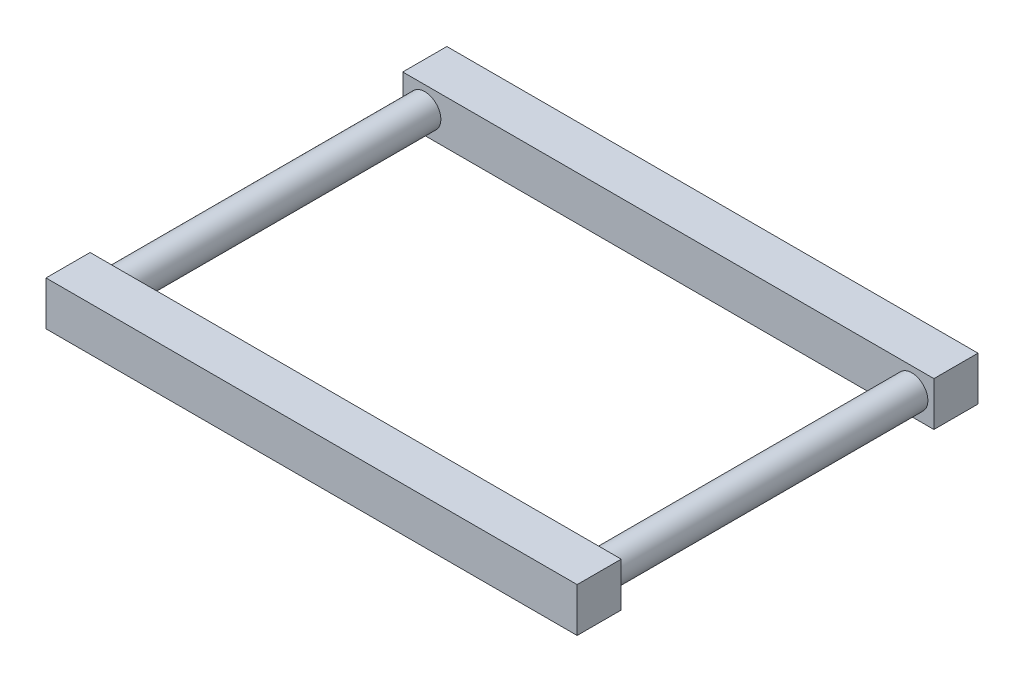
SolidWorks part; units mm, degrees
ref_plane "Front Plane" through (0, 0, 0) normal (0, 0, 1) x (1, 0, 0)
ref_plane "Top Plane" through (0, 0, 0) normal (0, 1, 0) x (1, 0, 0)
ref_plane "Right Plane" through (0, 0, 0) normal (1, 0, 0) x (0, 0, -1)
sketch "Sketch2" plane through (0, 0, 0) normal (0, 1, 0) x (1, 0, 0)
  line L0 (0, 0) -> (0, 198.12)
  line L1 (0, 0) -> (0, -198.12)
  line L2 (-20.32, 198.12) -> (-20.32, -198.12)
  line L3 (-20.32, 198.12) -> (20.32, 198.12)
  line L4 (0, 198.12) -> (0, -198.12)
  line L5 (-20.32, -198.12) -> (20.32, -198.12)
  line L6 (20.32, 198.12) -> (20.32, -198.12)
  dimension "D1" = 198.12
  dimension "D2" = 198.12
  dimension "D3" = 20.32
revolve "Revolve1" add sketch "Sketch2" angle 360 about L1 region at (-10.16, 0, 0)
sketch "Sketch3" plane through (0, 0, 0) normal (0, 1, 0) x (1, 0, 0)
  line L0 (0, -198.12) -> (-27.94, -198.12)
  line L1 (-20.32, -198.12) -> (20.32, -198.12) construction
  line L2 (0, -198.12) -> (27.94, -198.12)
  line L3 (-27.94, -198.12) -> (-27.94, -254)
  line L4 (-27.94, -254) -> (637.54, -254)
  line L5 (27.94, -198.12) -> (596.9, -198.12)
  line L6 (637.54, -254) -> (637.54, 254)
  line L7 (637.54, 0) -> (596.9, 0)
  line L8 (596.9, 198.12) -> (596.9, -198.12)
  line L9 (-22.352, 0) -> (22.352, 0) construction
  line L10 (-27.94, 254) -> (637.54, 254)
  line L11 (-27.94, 198.12) -> (-27.94, 254)
  line L12 (27.94, 198.12) -> (596.9, 198.12)
  line L13 (0, 198.12) -> (27.94, 198.12)
  line L14 (0, 198.12) -> (-27.94, 198.12)
  line L15 (637.54, -254) -> (645.16, -254)
  line L16 (596.9, -198.12) -> (645.16, -198.12)
  line L17 (645.16, -198.12) -> (645.16, -254)
  line L18 (637.54, 254) -> (645.16, 254)
  line L19 (645.16, 198.12) -> (645.16, 254)
  line L20 (596.9, 198.12) -> (645.16, 198.12)
  line L21 (617.22, 0) -> (617.22, -198.12)
  line L22 (617.22, 0) -> (617.22, 198.12)
  dimension "D1" = 27.94
  dimension "D2" = 27.94
  dimension "D3" = 55.88
  dimension "D4" = 665.48
  dimension "D5" = 40.64
  dimension "D6" = 7.62
extrude "Boss-Extrude1" add sketch "Sketch3" along normal blind 27.94 and the other way blind 27.94 contours L12 L20 L6 L10 L11 L14 L13 | L6 L20 L19 L18 | L16 L5 L2 L0 L3 L4 L6 | L17 L16 L6 L15 region at (304.8, 0, 226.06) region at (641.35, 0, 226.06) region at (304.8, 0, -226.06) region at (641.35, 0, -226.06)
revolve "Revolve3" add sketch "Sketch3<7>" angle 360 about L21 region at (627.38, 0, 99.06) region at (627.38, 0, -99.06)
sketch "Sketch3<7>" plane through (0, 0, 0) normal (0, 1, 0) x (1, 0, 0) same geometry as "Sketch3"
